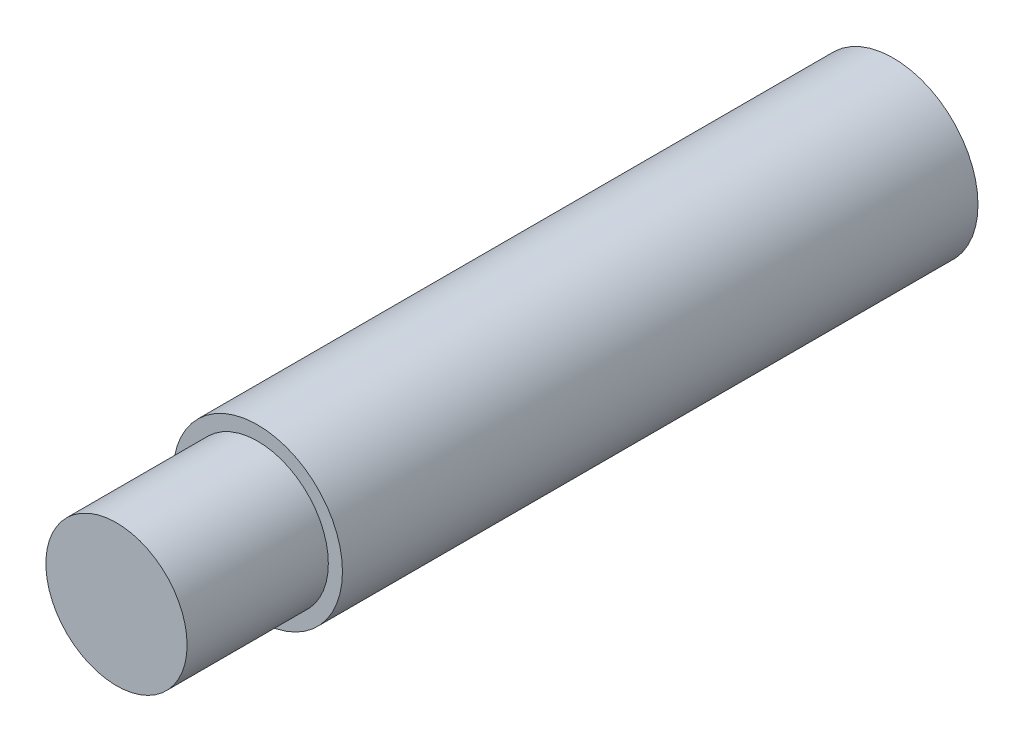
SolidWorks part; units mm, degrees
material "1060 Alloy"
ref_plane "Front Plane" through (0, 0, 0) normal (0, 0, 1) x (1, 0, 0)
ref_plane "Top Plane" through (0, 0, 0) normal (0, 1, 0) x (1, 0, 0)
ref_plane "Right Plane" through (0, 0, 0) normal (1, 0, 0) x (0, 0, -1)
sketch "Sketch1" plane through (0, 0, 0) normal (1, 0, 0) x (0, 0, -1)
  line L0 (0, 0) -> (45, 0)
  line L1 (45, 0) -> (45, 3.5)
  line L2 (45, 3.5) -> (55, 3.5)
  line L3 (55, 3.5) -> (55, 6)
  line L4 (55, 6) -> (10, 6)
  line L5 (10, 6) -> (10, 5)
  line L6 (10, 5) -> (0, 5)
  line L7 (0, 5) -> (0, 0)
  dimension "D1" = 10
  dimension "D2" = 5
  dimension "D3" = 6
  dimension "D4" = 3.5
  dimension "D5" = 45
  dimension "D6" = 10
revolve "Revolve1" add sketch "Sketch1" angle 360 about L0
